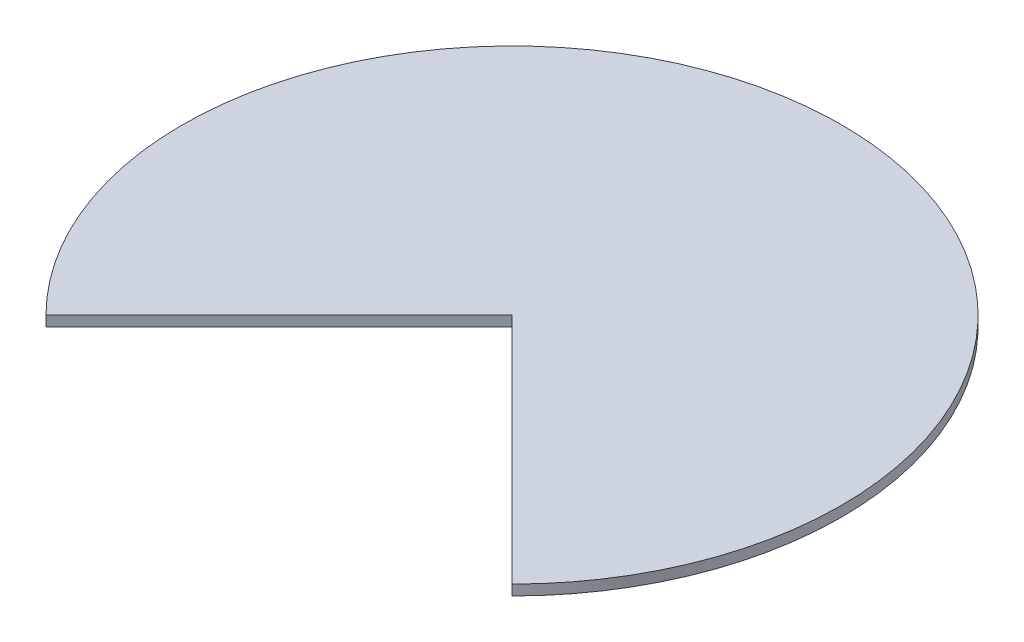
SolidWorks part; units mm, degrees
ref_plane "Front Plane" through (0, 0, 0) normal (0, 0, 1) x (1, 0, 0)
ref_plane "Top Plane" through (0, 0, 0) normal (0, 1, 0) x (1, 0, 0)
ref_plane "Right Plane" through (0, 0, 0) normal (1, 0, 0) x (0, 0, -1)
sketch "Sketch1" plane through (0, 0, 0) normal (0, 1, 0) x (1, 0, 0)
  line L0 (0, 0) -> (-143.6841, -143.6841)
  line L1 (0, 0) -> (143.6841, -143.6841)
  line L2 (0, 0) -> (0, -74434.7764) construction
  arc A0 (143.6841, -143.6841) -> (-143.6841, -143.6841) centre (0, 0) ccw
  dimension "D1" = 203.2
extrude "Boss-Extrude1" add sketch "Sketch1" along normal blind 6.35
